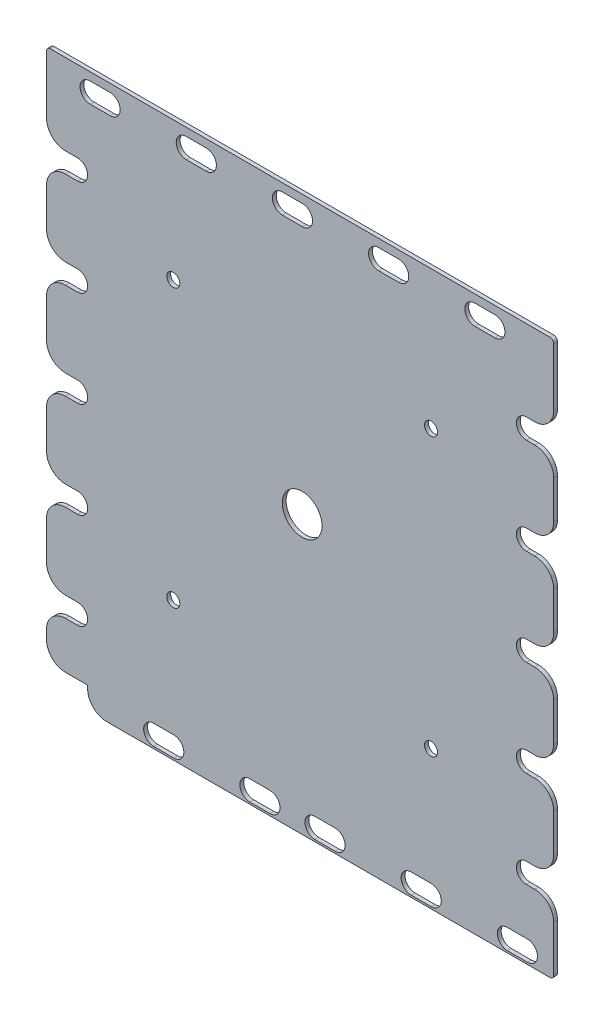
SolidWorks part; units mm, degrees
material "6061 Alloy"
ref_plane "Front Plane" through (0, 0, 0) normal (0, 0, 1) x (1, 0, 0)
ref_plane "Top Plane" through (0, 0, 0) normal (0, 1, 0) x (1, 0, 0)
ref_plane "Right Plane" through (0, 0, 0) normal (1, 0, 0) x (0, 0, -1)
sketch "Sketch1" plane through (0, 0, 0) normal (0, 0, 1) x (1, 0, 0)
  line L0 (0, 0) -> (0, -146.4313)
  line L3 (0, -146.4313) -> (135.0197, -146.4313)
  line L5 (0, 0) -> (135.0197, 0)
  line L6 (135.0197, -146.4313) -> (135.0197, 0)
  line L7 (67.5099, 0) -> (67.5099, -146.4313) construction
  line L8 (16.8049, -2.1125) -> (11.5049, -2.1125)
  line L9 (16.8049, -7.4125) -> (11.5049, -7.4125)
  line L10 (76.2, -145.9063) -> (70.9, -145.9063)
  line L11 (76.2, -140.6063) -> (70.9, -140.6063)
  line L12 (101.6, -140.6063) -> (96.3, -140.6063)
  line L13 (101.6, -145.9063) -> (96.3, -145.9063)
  line L14 (42.2049, -2.1125) -> (36.9049, -2.1125)
  line L15 (42.2049, -7.4125) -> (36.9049, -7.4125)
  line L16 (67.6049, -2.1125) -> (62.3049, -2.1125)
  line L17 (67.6049, -7.4125) -> (62.3049, -7.4125)
  line L18 (93.0049, -2.1125) -> (87.7049, -2.1125)
  line L19 (93.0049, -7.4125) -> (87.7049, -7.4125)
  line L20 (118.4049, -2.1125) -> (113.1049, -2.1125)
  line L21 (118.4049, -7.4125) -> (113.1049, -7.4125)
  line L22 (127, -140.6063) -> (121.7, -140.6063)
  line L23 (127, -145.9063) -> (121.7, -145.9063)
  line L25 (8.2099, -97.5531) -> (2.9099, -97.5531)
  line L26 (8.2099, -102.8531) -> (2.9099, -102.8531)
  line L27 (8.2099, -72.1531) -> (2.9099, -72.1531)
  line L28 (8.2099, -77.4531) -> (2.9099, -77.4531)
  line L29 (8.2099, -46.7531) -> (2.9099, -46.7531)
  line L30 (8.2099, -52.0531) -> (2.9099, -52.0531)
  line L31 (8.2099, -21.3531) -> (2.9099, -21.3531)
  line L32 (8.2099, -26.6531) -> (2.9099, -26.6531)
  line L33 (132.0349, -122.9531) -> (126.7349, -122.9531)
  line L34 (132.0349, -128.2531) -> (126.7349, -128.2531)
  line L35 (132.0349, -97.5531) -> (126.7349, -97.5531)
  line L36 (132.0349, -102.8531) -> (126.7349, -102.8531)
  line L37 (132.0349, -72.1531) -> (126.7349, -72.1531)
  line L38 (8.2099, -122.9531) -> (2.9099, -122.9531)
  line L39 (8.2099, -128.2531) -> (2.9099, -128.2531)
  line L40 (132.0349, -77.4531) -> (126.7349, -77.4531)
  line L41 (132.0349, -46.7531) -> (126.7349, -46.7531)
  line L42 (8.2099, -140.6063) -> (2.9099, -140.6063)
  line L43 (8.2099, -145.9063) -> (2.9099, -145.9063)
  line L44 (33.6099, -140.6063) -> (28.3099, -140.6063)
  line L45 (33.6099, -145.9063) -> (28.3099, -145.9063)
  line L46 (59.0099, -140.6063) -> (53.7099, -140.6063)
  line L47 (59.0099, -145.9063) -> (53.7099, -145.9063)
  line L48 (132.0349, -52.0531) -> (126.7349, -52.0531)
  line L49 (132.0349, -21.3531) -> (126.7349, -21.3531)
  line L50 (132.0349, -26.6531) -> (126.7349, -26.6531)
  line L54 (0, 0) -> (0, -146.4313)
  line L55 (135.0197, -146.4313) -> (135.0197, 0)
  line L56 (0, -146.4313) -> (135.0197, -146.4313)
  circle A41 centre (8.2099, -125.6031) radius 2.65
  circle A42 centre (8.2099, -143.2563) radius 2.65
  circle A49 centre (33.6099, -143.2563) radius 2.65
  circle A50 centre (59.0099, -143.2563) radius 2.65
  circle A69 centre (93.0049, -4.7625) radius 2.65
  circle A70 centre (67.6049, -4.7625) radius 2.65
  circle A71 centre (42.2049, -4.7625) radius 2.65
  circle A73 centre (118.4049, -4.7625) radius 2.65
  circle A74 centre (16.8049, -4.7625) radius 2.65
  circle A81 centre (11.5049, -4.7625) radius 2.65
  circle A85 centre (36.9049, -4.7625) radius 2.65
  circle A86 centre (62.3049, -4.7625) radius 2.65
  circle A87 centre (87.7049, -4.7625) radius 2.65
  circle A88 centre (113.1049, -4.7625) radius 2.65
  circle A97 centre (2.9099, -125.6031) radius 2.65
  circle A99 centre (2.9099, -143.2563) radius 2.65
  circle A100 centre (28.3099, -143.2563) radius 2.65
  circle A101 centre (53.7099, -143.2563) radius 2.65
  circle A105 centre (67.5099, -73.2156) radius 5.25
  circle A106 centre (84.4099, -143.2563) radius 2.65
  circle A107 centre (109.8099, -143.2563) radius 2.65
  circle A108 centre (76.2, -143.2563) radius 2.65
  circle A109 centre (70.9, -143.2563) radius 2.65
  circle A110 centre (96.3, -143.2563) radius 2.65
  circle A111 centre (101.6, -143.2563) radius 2.65
  circle A112 centre (121.7, -143.2563) radius 2.65
  circle A113 centre (127, -143.2563) radius 2.65
  circle A114 centre (2.9099, -100.2031) radius 2.65
  circle A115 centre (8.2099, -100.2031) radius 2.65
  circle A116 centre (2.9099, -74.8031) radius 2.65
  circle A117 centre (8.2099, -74.8031) radius 2.65
  circle A118 centre (2.9099, -49.4031) radius 2.65
  circle A119 centre (8.2099, -49.4031) radius 2.65
  circle A120 centre (2.9099, -24.0031) radius 2.65
  circle A121 centre (8.2099, -24.0031) radius 2.65
  circle A122 centre (132.0349, -125.6031) radius 2.65
  circle A123 centre (126.7349, -125.6031) radius 2.65
  circle A124 centre (126.7349, -100.2031) radius 2.65
  circle A125 centre (132.0349, -100.2031) radius 2.65
  circle A126 centre (126.7349, -74.8031) radius 2.65
  circle A127 centre (132.0349, -74.8031) radius 2.65
  circle A128 centre (126.7349, -49.4031) radius 2.65
  circle A129 centre (132.0349, -49.4031) radius 2.65
  circle A130 centre (126.7349, -24.0031) radius 2.65
  circle A131 centre (132.0349, -24.0031) radius 2.65
  dimension "D8" = 5.3
  dimension "D21" = 5.3
  dimension "D31" = 10.5
  dimension "D33" = 5.3
  dimension "D9" = 5.3
  dimension "D1" = 135.0197
  dimension "D2" = 146.4313
  dimension "D6" = 8.2099
  dimension "D7" = 3.175
  dimension "D10" = 25.4
  dimension "D23" = 25.4
  dimension "D27" = 25.4
  dimension "D28" = 0
  dimension "D29" = 0
  dimension "D30" = 73.2156
  dimension "D13" = 25.4
  dimension "D5" = 17.1901
  dimension "D15" = 25.4
  dimension "D19" = 25.4
  dimension "D25" = 25.4
  dimension "D12" = 4.7625
  dimension "D17" = 16.8049
  dimension "D20" = 132.0349
  dimension "D4" = 24.0031
  dimension "D32" = 24.0031
  dimension "D34" = 8.2099
  dimension "D14" = 5
  dimension "D16" = 5
  dimension "D22" = 5
  dimension "D26" = 3
  dimension "D11" = 3
  dimension "D18" = 5
  dimension "D24" = 5
extrude "Boss-Extrude1" add sketch "Sketch1" along normal blind 1.016
sketch "Sketch3" plane through (0, 0, 1.016) normal (0, 0, 1) x (1, 0, 0)
  line L0 (133.9197, 0) -> (133.9197, -146.4313)
  line L1 (0, 0) -> (135.0197, 0) construction
  line L2 (0, -146.4313) -> (135.0197, -146.4313) construction
  line L3 (135.0197, -146.4313) -> (135.0197, 0) construction
  line L4 (133.9197, 0) -> (135.0197, 0)
  line L5 (135.0197, 0) -> (135.0197, -146.4313)
  line L6 (135.0197, -146.4313) -> (133.9197, -146.4313)
  dimension "D1" = 1.1
extrude "Cut-Extrude1" cut sketch "Sketch3" against normal up to surface (1.016 mm away) up to face at (64.9549, -4.7625, 0)
fillet "Fillet1" radius 1 4 edges at (0, -146.4313, 0.508) (0, 0, 0.508) (133.9197, -146.4313, 0.508) (133.9197, 0, 0.508)
sketch "Sketch4" plane through (0, 0, 1.016) normal (0, 0, 1) x (1, 0, 0)
  line L0 (133.9197, -1) -> (0, -1) construction
  line L1 (33.4799, -36.6078) -> (101.5398, -36.6078) construction
  line L2 (33.4799, -36.6078) -> (33.4799, -109.8235) construction
  line L3 (33.4799, -109.8235) -> (101.5398, -109.8235) construction
  line L4 (101.5398, -36.6078) -> (101.5398, -109.8235) construction
  line L5 (33.4799, -36.6078) -> (101.5398, -109.8235) construction
  line L6 (33.4799, -109.8235) -> (101.5398, -36.6078) construction
  line L7 (1, 0) -> (1, -146.4313) construction
  line L8 (0, -1) -> (0, -145.4313) construction
  line L9 (2.9099, -21.3531) -> (0, -21.3531)
  line L10 (2.9099, -21.3531) -> (2.9099, -26.6531)
  line L11 (2.9099, -26.6531) -> (0, -26.6531)
  line L12 (0, -21.3531) -> (0, -26.6531)
  line L13 (2.9099, -46.7531) -> (2.9099, -52.0531)
  line L14 (2.9099, -46.7531) -> (0, -46.7531)
  line L15 (0, -46.7531) -> (0, -52.0531)
  line L16 (2.9099, -52.0531) -> (0, -52.0531)
  line L17 (2.9099, -72.1531) -> (2.9099, -77.4531)
  line L18 (2.9099, -72.1531) -> (0, -72.1531)
  line L19 (0, -72.1531) -> (0, -77.4531)
  line L20 (2.9099, -77.4531) -> (0, -77.4531)
  line L21 (2.9099, -97.5531) -> (2.9099, -102.8531)
  line L22 (2.9099, -97.5531) -> (0, -97.5531)
  line L23 (0, -97.5531) -> (0, -102.8531)
  line L24 (2.9099, -102.8531) -> (0, -102.8531)
  line L25 (2.9099, -122.9531) -> (2.9099, -128.2531)
  line L26 (2.9099, -122.9531) -> (0, -122.9531)
  line L27 (0, -122.9531) -> (0, -128.2531)
  line L28 (2.9099, -128.2531) -> (0, -128.2531)
  line L29 (1, -146.4313) -> (132.9197, -146.4313) construction
  line L30 (10.8599, -140.6063) -> (0, -140.6063)
  line L31 (10.8599, -140.6063) -> (10.8599, -146.4313)
  line L32 (10.8599, -146.4313) -> (0, -146.4313)
  line L33 (0, -140.6063) -> (0, -146.4313)
  line L34 (8.2099, -140.6063) -> (2.9099, -140.6063) construction
  arc A0 (8.2099, -145.9063) -> (8.2099, -140.6063) centre (8.2099, -143.2563) ccw construction
  circle A3 centre (33.4799, -36.6078) radius 1.725
  circle A4 centre (101.5398, -36.6078) radius 1.725
  circle A5 centre (101.5398, -109.8235) radius 1.725
  circle A6 centre (33.4799, -109.8235) radius 1.725
  point P4 (67.5099, -73.2156)
  point P23 (2.9099, -24.0031)
  point P24 (2.9099, -49.4031)
  point P49 (2.9099, -145.9063)
  point P51 (-0.5846, -140.6063)
  point P52 (2.9099, -145.9063)
  point P53 (0, 0)
  point P54 (2.9099, -146.4313)
  point P57 (0, 0)
  point P58 (10.9341, -140.2121)
  dimension "D2" = 146.4313
  dimension "D3" = 3.45
  dimension "D1" = 133.9197
  dimension "D4" = 33.4799
  dimension "D5" = 36.6078
  dimension "D7" = 25.4
  dimension "D6" = 5
extrude "Cut-Extrude2" cut sketch "Sketch4" against normal through all both
fillet "Fillet2" radius 5 52 edges at (133.0562, -26.4484, 0) (133.0562, -51.8484, 0) (133.0562, -77.2484, 0) (133.0562, -102.6484, 0) (133.0562, -128.0484, 0) (132.0349, -21.3531, 0.508) (132.0349, -26.6531, 0.508) (132.0349, -46.7531, 0.508) (132.0349, -52.0531, 0.508) (132.0349, -72.1531, 0.508) (132.0349, -77.4531, 0.508) (132.0349, -97.5531, 0.508) (132.0349, -102.8531, 0.508) (132.0349, -128.2531, 0.508) (132.0349, -122.9531, 0.508) (133.0562, -123.1578, 0) (133.0562, -97.7578, 0) (133.0562, -72.3578, 0) (133.0562, -46.9578, 0) (133.0562, -21.5578, 0) (133.0562, -123.1578, 1.016) (133.0562, -97.7578, 1.016) (133.0562, -72.3578, 1.016) (133.0562, -46.9578, 1.016) (133.0562, -21.5578, 1.016) (133.9197, -22.1404, 0.508) (133.9197, -25.8659, 0.508) (133.9197, -47.5404, 0.508) (133.9197, -51.2659, 0.508) (133.9197, -72.9404, 0.508) (133.9197, -76.6659, 0.508) (133.9197, -98.3404, 0.508) (133.9197, -102.0659, 0.508) (133.9197, -123.7404, 0.508) (133.9197, -127.4659, 0.508) (133.0562, -128.0484, 1.016) (0, -140.6063, 0.508) (133.0562, -102.6484, 1.016) (10.8599, -146.4313, 0.508) (0, -26.6531, 0.508) (133.0562, -77.2484, 1.016) (0, -21.3531, 0.508) (0, -46.7531, 0.508) (0, -52.0531, 0.508) (0, -72.1531, 0.508) (0, -77.4531, 0.508) (0, -97.5531, 0.508) (133.0562, -51.8484, 1.016) (0, -102.8531, 0.508) (0, -122.9531, 0.508) (0, -128.2531, 0.508) (133.0562, -26.4484, 1.016)
equation "\"D29@Sketch1\"= \"D28@Sketch1\""
equation "\"D30@Sketch1\"=\"D2@Sketch1\"/2"
equation "\"D13@Sketch1\"=\"D23@Sketch1\""
equation "\"Hole_Offset\"= 1.2083"
equation "\"D6@Sketch1\"=8.209+0.0009"
equation "\"D15@Sketch1\"=\"D27@Sketch1\""
equation "\"D25@Sketch1\"=\"D19@Sketch1\""
equation "\"D17@Sketch1\"=16.8046+0.0003"
equation "\"D2@Sketch1\"=146.4315890mm-0.0003"
equation "\"D4@Sketch4\"=\"D1@Sketch4\"/4"
equation "\"D5@Sketch4\"=\"D2@Sketch4\"/4"
equation "\"D8@Sketch1\"=\"D9@Sketch1\""
